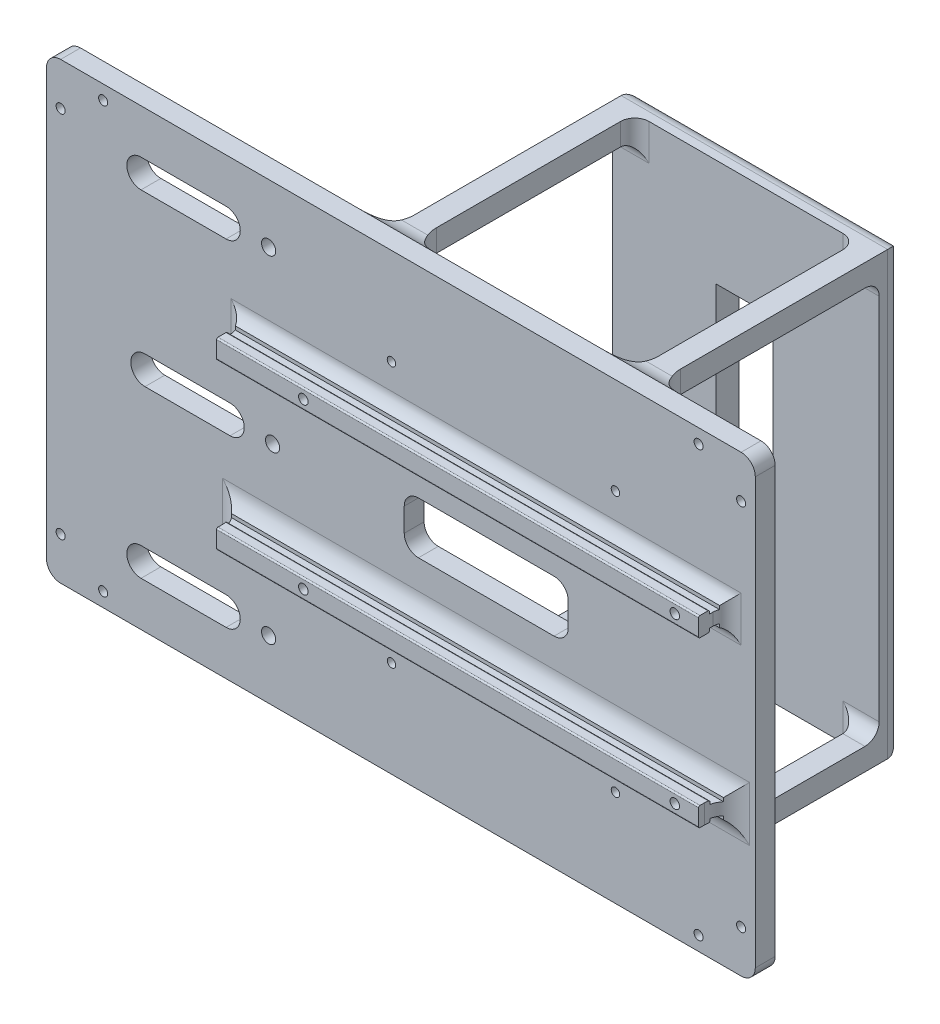
SolidWorks part; units mm, degrees
ref_plane "前视基准面" through (0, 0, 0) normal (0, 0, 1) x (1, 0, 0)
ref_plane "上视基准面" through (0, 0, 0) normal (0, 1, 0) x (1, 0, 0)
ref_plane "右视基准面" through (0, 0, 0) normal (1, 0, 0) x (0, 0, -1)
other "Configuration Table"
sketch "草图1" plane through (0, 0, 0) normal (0, 0, 1) x (1, 0, 0)
  line L0 (0, 0) -> (0, 26371.7997) construction
  line L1 (0, 0) -> (26371.7997, 0) construction
  line L3 (-125, 80) -> (125, 80)
  line L4 (-125, 80) -> (-125, -80)
  line L5 (-125, -80) -> (125, -80)
  line L6 (125, 80) -> (125, -80)
  line L7 (-125, 80) -> (125, -80) construction
  line L8 (-125, -80) -> (125, 80) construction
  point P5 (0, 0)
  dimension "D1" = 250
  dimension "D2" = 160
extrude "凸台-拉伸1" add sketch "草图1" along normal blind 7
sketch "草图2" plane through (0, 0, 7) normal (0, 0, 1) x (1, 0, 0)
  line L0 (0, 0) -> (50000, 0) construction
  line L1 (0, 0) -> (0, 50000) construction
  line L2 (125, -80) -> (125, 80) construction
  line L3 (-55, 32.4) -> (115, 32.4)
  line L4 (-55, 32.4) -> (-55, 25.6)
  line L5 (-55, 25.6) -> (115, 25.6)
  line L6 (115, 32.4) -> (115, 25.6)
  line L7 (-55, 32.4) -> (115, 25.6) construction
  line L8 (-55, 25.6) -> (115, 32.4) construction
  line L9 (-55, -25.6) -> (115, -25.6)
  line L10 (115, -32.4) -> (115, -25.6)
  line L11 (-55, -32.4) -> (-55, -25.6)
  line L12 (-55, -32.4) -> (115, -32.4)
  point P5 (30, 29)
  dimension "D1" = 29
  dimension "D2" = 170
  dimension "D3" = 10
  dimension "D4" = 6.8
extrude "凸台-拉伸2" add sketch "草图2" along normal blind 10
sketch "草图3" plane through (115, 0, 0) normal (1, 0, 0) x (0, 0, -1)
  line L0 (-17, 29) -> (-7, 29) construction
  line L1 (-17, 25.6) -> (-17, 32.4) construction
  line L2 (-7, 25.6) -> (-7, 32.4) construction
  line L3 (-17, 32.4) -> (-7, 32.4) construction
  line L4 (-13.2, 32.4) -> (-10, 32.4)
  line L5 (-13.2, 32.4) -> (-13.2, 31.15)
  line L6 (-13.2, 31.15) -> (-10, 31.15)
  line L7 (-10, 32.4) -> (-10, 31.15)
  line L8 (-13.2, 26.85) -> (-10, 26.85)
  line L9 (-10, 25.6) -> (-10, 26.85)
  line L10 (-13.2, 25.6) -> (-13.2, 26.85)
  line L11 (-13.2, 25.6) -> (-10, 25.6)
  dimension "D1" = 3.8
  dimension "D2" = 3.2
  dimension "D3" = 4.3
extrude "切除-拉伸1" cut sketch "草图3" against normal through all
fillet "圆角1" radius 0.5 4 edges at (30, 25.6, 13.2) (30, 25.6, 17) (30, 32.4, 17) (30, 32.4, 13.2)
sketch "草图4" plane through (115, 0, 0) normal (1, 0, 0) x (0, 0, -1)
  line L0 (-17, -29) -> (-7, -29) construction
  line L1 (-17, -32.4) -> (-17, -25.6) construction
  line L2 (-7, -32.4) -> (-7, -25.6) construction
  line L3 (-17, -25.6) -> (-7, -25.6) construction
  line L4 (-13.2, -25.6) -> (-10, -25.6)
  line L5 (-13.2, -25.6) -> (-13.2, -26.85)
  line L6 (-13.2, -26.85) -> (-10, -26.85)
  line L7 (-10, -25.6) -> (-10, -26.85)
  line L8 (-10, -32.4) -> (-10, -31.15)
  line L9 (-13.2, -31.15) -> (-10, -31.15)
  line L10 (-13.2, -32.4) -> (-13.2, -31.15)
  line L11 (-13.2, -32.4) -> (-10, -32.4)
  dimension "D1" = 3.8
  dimension "D2" = 3.2
  dimension "D3" = 4.3
extrude "切除-拉伸2" cut sketch "草图4" against normal through all
fillet "圆角2" radius 0.5 4 edges at (30, -32.4, 13.2) (30, -32.4, 17) (30, -25.6, 17) (30, -25.6, 13.2)
fillet "圆角3" radius 5 2 edges at (30, 25.6, 7) (30, 32.4, 7)
fillet "圆角4" radius 5 2 edges at (115, 29, 7) (-55, 29, 7)
fillet "圆角5" radius 8 4 edges at (-55, -29, 7) (115, -29, 7) (30, -25.6, 7) (30, -32.4, 7)
sketch "草图5" plane through (0, 0, 0) normal (0, 0, -1) x (-1, 0, 0)
  line L0 (-125, 0) -> (131.1555, 0) construction
  line L1 (-125, -80) -> (-125, 80) construction
  line L2 (-30, 29) -> (-115, 29) construction
  line L3 (-115, 32.4) -> (-115, 25.6) construction
  line L4 (-115, 29) -> (55, 29) construction
  line L5 (55, 32.4) -> (55, 25.6) construction
  circle A0 centre (-106.6, 29) radius 1.675
  circle A1 centre (24.4, 29) radius 1.675
  circle A2 centre (24.4, -29) radius 1.675
  circle A3 centre (-106.6, -29) radius 1.675
  dimension "D1" = 8.4
  dimension "D2" = 3.35
  dimension "D3" = 3.35
  dimension "D4" = 131
extrude "切除-拉伸3" cut sketch "草图5" against normal through all
sketch "草图6" plane through (0, 0, 0) normal (0, 0, -1) x (-1, 0, 0)
  line L0 (-125, 80) -> (-95, 80)
  line L1 (-125, 80) -> (125, 80) construction
  line L2 (-95, 80) -> (-95, 70)
  line L3 (-95, 70) -> (-115, 70)
  line L4 (-115, 70) -> (-115, 60)
  line L5 (-115, 60) -> (-125, 60)
  line L6 (-125, -80) -> (-125, 80) construction
  line L7 (-125, 60) -> (-125, 80)
  line L8 (0, 0) -> (50000, 0) construction
  line L9 (125, 80) -> (95, 80)
  line L10 (95, 80) -> (95, 70)
  line L11 (95, 70) -> (115, 70)
  line L12 (115, 70) -> (115, 60)
  line L13 (115, 60) -> (125, 60)
  line L14 (125, 80) -> (125, -80) construction
  line L15 (125, 60) -> (125, 80)
  line L16 (-125, -60) -> (-125, -80)
  line L17 (-115, -60) -> (-125, -60)
  line L18 (-115, -70) -> (-115, -60)
  line L19 (-95, -70) -> (-115, -70)
  line L20 (-95, -80) -> (-95, -70)
  line L21 (-125, -80) -> (-95, -80)
  line L22 (125, -60) -> (125, -80)
  line L23 (115, -60) -> (125, -60)
  line L24 (115, -70) -> (115, -60)
  line L25 (95, -70) -> (115, -70)
  line L26 (95, -80) -> (95, -70)
  line L27 (125, -80) -> (95, -80)
  circle A0 centre (-120, 65) radius 1.6
  circle A1 centre (-105, 75) radius 1.6
  circle A2 centre (105, 75) radius 1.6
  circle A3 centre (120, 65) radius 1.6
  circle A4 centre (120, -65) radius 1.6
  circle A5 centre (105, -75) radius 1.6
  circle A6 centre (-105, -75) radius 1.6
  circle A7 centre (-120, -65) radius 1.6
  dimension "D9" = 3.2
  dimension "D10" = 5
  dimension "D11" = 5
  dimension "D12" = 3.2
  dimension "D13" = 5
  dimension "D14" = 10
  dimension "D15" = 5
  dimension "D16" = 10
  dimension "D17" = 3.2
  dimension "D18" = 5
  dimension "D19" = 5
  dimension "D20" = 3.2
  dimension "D1" = 30
  dimension "D2" = 20
  dimension "D3" = 10
  dimension "D4" = 10
  dimension "D5" = 30
  dimension "D6" = 20
  dimension "D7" = 10
  dimension "D8" = 10
extrude "切除-拉伸4" cut sketch "草图6" against normal through all contours A5 | A4 | A3 | A2 | A1 | A0 | A7 | A6
sketch "草图8" plane through (0, 0, 0) normal (0, 0, -1) x (-1, 0, 0)
  line L28 (61.653, 64.319) -> (91.653, 64.319)
  line L29 (61.653, 54.319) -> (91.653, 54.319)
  line L38 (61.653, 64.319) -> (61.653, 54.319) construction
  line L39 (91.653, 64.319) -> (91.653, 54.319) construction
  line L40 (61.653, 64.319) -> (91.653, 54.319) construction
  line L41 (61.653, 54.319) -> (91.653, 64.319) construction
  line L64 (60.2593, 4.9129) -> (90.2593, 4.9129)
  line L70 (61.653, -54.319) -> (91.653, -64.319) construction
  line L71 (61.653, -64.319) -> (91.653, -54.319) construction
  line L72 (91.653, -64.319) -> (91.653, -54.319) construction
  line L73 (61.653, -64.319) -> (61.653, -54.319) construction
  line L74 (61.653, -54.319) -> (91.653, -54.319)
  line L75 (61.653, -64.319) -> (91.653, -64.319)
  line L78 (60.2593, -5.0871) -> (90.2593, -5.0871)
  line L79 (60.2593, 4.9129) -> (60.2593, -5.0871) construction
  line L80 (90.2593, 4.9129) -> (90.2593, -5.0871) construction
  line L81 (60.2593, 4.9129) -> (90.2593, -5.0871) construction
  line L82 (60.2593, -5.0871) -> (90.2593, 4.9129) construction
  arc A10 (61.653, 54.319) -> (61.653, 64.319) centre (61.653, 59.319) cw
  arc A11 (91.653, 54.319) -> (91.653, 64.319) centre (91.653, 59.319) ccw
  circle A25 centre (46.653, 59.319) radius 2.5
  circle A36 centre (46.653, -59.319) radius 2.5
  arc A37 (91.653, -54.319) -> (91.653, -64.319) centre (91.653, -59.319) cw
  arc A38 (61.653, -54.319) -> (61.653, -64.319) centre (61.653, -59.319) ccw
  arc A39 (60.2593, -5.0871) -> (60.2593, 4.9129) centre (60.2593, -0.0871) cw
  arc A40 (90.2593, -5.0871) -> (90.2593, 4.9129) centre (90.2593, -0.0871) ccw
  circle A41 centre (45.2593, -0.0871) radius 2.5
  point P0 (75.2593, -0.0871)
  point P9 (-5, -50)
  point P10 (-85, -50)
  point P14 (-5, 50)
  point P17 (-85, 50)
  point P18 (-5, 0)
  point P34 (76.653, -59.319)
  point P41 (76.653, 59.319)
extrude "切除-拉伸5" cut sketch "草图8" against normal through all
fillet "圆角6" radius 5 4 edges at (-125, 80, 3.5) (125, 80, 3.5) (125, -80, 3.5) (-125, -80, 3.5)
sketch "草图9" plane through (0, 0, 0) normal (0, 0, -1) x (-1, 0, 0)
  circle A0 centre (-106.6, 29) radius 3.5
  circle A1 centre (24.4, 29) radius 3.5
  circle A2 centre (-106.6, -29) radius 3.5
  circle A3 centre (24.4, -29) radius 3.5
  dimension "D1" = 7
  dimension "D2" = 7
  dimension "D3" = 7
  dimension "D4" = 7
extrude "切除-拉伸6" cut sketch "草图9" against normal blind 3
sketch "草图15" plane through (0, 0, 0) normal (0, 0, -1) x (-1, 0, 0)
  line L0 (-200000, 0) -> (250000, 0) construction
  line L1 (-97.69, 55) -> (12.31, 55) construction
  line L2 (-97.69, 55) -> (-97.69, -55) construction
  line L3 (-97.69, -55) -> (12.31, -55) construction
  line L4 (12.31, 55) -> (12.31, -55) construction
  line L5 (-97.69, 55) -> (12.31, -55) construction
  line L6 (-97.69, -55) -> (12.31, 55) construction
  line L8 (-75.69, 46) -> (3.31, 46) construction
  line L9 (-75.69, 46) -> (-75.69, -46) construction
  line L10 (-75.69, -46) -> (3.31, -46) construction
  line L11 (3.31, 46) -> (3.31, -46) construction
  line L12 (-75.69, 46) -> (3.31, -46) construction
  line L13 (-75.69, -46) -> (3.31, 46) construction
  circle A0 centre (-75.69, 46) radius 1.5
  circle A1 centre (3.31, 46) radius 1.5
  circle A2 centre (-75.69, -46) radius 1.5
  circle A3 centre (3.31, -46) radius 1.5
  point P0 (-42.69, 0)
  point P8 (-36.19, 0)
  dimension "D3" = 9
  dimension "D1" = 110
  dimension "D2" = 110
  dimension "D4" = 92
  dimension "D5" = 79
extrude "切除-拉伸7" cut sketch "草图15" against normal up to next
sketch "草图17" plane through (0, 0, 0) normal (0, 0, -1) x (-1, 0, 0)
  line L0 (-200000, 0) -> (250000, 0) construction
  line L1 (-97.69, 55) -> (12.31, 55) construction
  line L2 (-97.69, 55) -> (-97.69, -55) construction
  line L3 (-97.69, -55) -> (12.31, -55) construction
  line L4 (12.31, 55) -> (12.31, -55) construction
  line L5 (-97.69, 55) -> (12.31, -55) construction
  line L6 (-97.69, -55) -> (12.31, 55) construction
  line L7 (-26.0576, 0) -> (194.9293, 0) construction
  line L8 (-81.69, 77.8) -> (-73.89, 77.8)
  line L9 (-81.69, 77.8) -> (-81.69, 70)
  line L10 (-81.69, 70) -> (-73.89, 70)
  line L11 (-73.89, 77.8) -> (-73.89, 70)
  line L12 (-81.69, 77.8) -> (-73.89, 70) construction
  line L13 (-81.69, 70) -> (-73.89, 77.8) construction
  line L14 (4.51, -70) -> (12.31, -77.8) construction
  line L15 (4.51, 77.8) -> (12.31, 77.8)
  line L16 (4.51, 77.8) -> (4.51, 70)
  line L17 (4.51, 70) -> (12.31, 70)
  line L18 (12.31, 77.8) -> (12.31, 70)
  line L19 (4.51, 77.8) -> (12.31, 70) construction
  line L20 (4.51, 70) -> (12.31, 77.8) construction
  line L21 (4.51, -77.8) -> (12.31, -70) construction
  line L22 (-81.69, -70) -> (-73.89, -77.8) construction
  line L23 (-81.69, -77.8) -> (-73.89, -70) construction
  line L24 (12.31, -77.8) -> (12.31, -70)
  line L25 (4.51, -70) -> (12.31, -70)
  line L26 (4.51, -77.8) -> (4.51, -70)
  line L27 (4.51, -77.8) -> (12.31, -77.8)
  line L28 (-73.89, -77.8) -> (-73.89, -70)
  line L29 (-81.69, -70) -> (-73.89, -70)
  line L30 (-81.69, -77.8) -> (-81.69, -70)
  line L31 (-81.69, -77.8) -> (-73.89, -77.8)
  circle A0 centre (3.31, 46) radius 1.5 construction
  circle A1 centre (3.31, 46) radius 1.5 construction
  point P0 (-42.69, 0)
  point P10 (-77.79, 73.9)
  point P15 (8.41, 73.9)
  point P30 (8.41, -73.9)
  point P31 (-77.79, -73.9)
  dimension "D1" = 110
  dimension "D2" = 110
  dimension "D3" = 9
  dimension "D4" = 16
  dimension "D5" = 7.8
  dimension "D6" = 7.8
  dimension "D7" = 15
  dimension "D8" = 7.8
  dimension "D9" = 7.8
extrude "凸台-拉伸3" add sketch "草图17" along normal blind 80
sketch "草图18" plane through (0, 0, -80) normal (0, 0, -1) x (-1, 0, 0)
  line L0 (-81.69, 77.8) -> (12.31, 77.8)
  line L1 (12.31, 77.8) -> (12.31, -77.8)
  line L2 (12.31, -77.8) -> (-81.69, -77.8)
  line L3 (-81.69, -77.8) -> (-81.69, 77.8)
extrude "凸台-拉伸4" add sketch "草图18" along normal blind 8
sketch "草图19" plane through (0, 0, -88) normal (0, 0, -1) x (-1, 0, 0)
  line L0 (-80.69, 77.8) -> (12.31, -77.8) construction
  line L4 (-59.19, 50) -> (-9.19, 50) construction
  line L5 (-59.19, 50) -> (-59.19, -50) construction
  line L6 (-59.19, -50) -> (-9.19, -50) construction
  line L7 (-9.19, 50) -> (-9.19, -50) construction
  line L8 (-59.19, 50) -> (-9.19, -50) construction
  line L9 (-59.19, -50) -> (-9.19, 50) construction
  circle A0 centre (-59.19, 50) radius 2
  circle A1 centre (-9.19, 50) radius 2
  circle A2 centre (-59.19, -50) radius 2
  circle A3 centre (-9.19, -50) radius 2
  dimension "D1" = 50
  dimension "D2" = 100
extrude "切除-拉伸8" cut sketch "草图19" against normal blind 5
sketch "草图20" plane through (0, 0, 0) normal (0, 0, -1) x (-1, 0, 0)
  line L0 (-200000, 0) -> (250000, 0) construction
  line L1 (-1.1877, 9.1461) -> (-59.0259, 9.1461)
  line L2 (-1.1877, 9.1461) -> (-1.1877, -9.1461)
  line L3 (-1.1877, -9.1461) -> (-59.0259, -9.1461)
  line L4 (-59.0259, 9.1461) -> (-59.0259, -9.1461)
  line L5 (-1.1877, 9.1461) -> (-59.0259, -9.1461) construction
  line L6 (-1.1877, -9.1461) -> (-59.0259, 9.1461) construction
  point P0 (-30.1068, 0)
extrude "切除-拉伸9" cut sketch "草图20" against normal up to next
fillet "圆角7" radius 5 4 edges at (59.0259, -9.1461, 3.5) (1.1877, -9.1461, 3.5) (59.0259, 9.1461, 3.5) (1.1877, 9.1461, 3.5)
fillet "圆角10" radius 5 2 edges at (73.89, 73.9, -80) (-4.51, 73.9, -80)
fillet "圆角12" radius 5 2 edges at (77.79, -70, -80) (75.29, 70, -80)
fillet "圆角13" radius 5 4 edges at (-5.91, 70, -80) (-4.51, -73.9, -80) (-8.41, -70, -80) (73.89, -71.4, -80)
fillet "圆角14" radius 5 4 edges at (34.69, -77.8, -88) (81.69, 0, -88) (-12.31, 0, -88) (34.69, 77.8, -88)
sketch "草图21" plane through (0, 0, -88) normal (0, 0, -1) x (-1, 0, 0)
  line L0 (-200000, 0) -> (250000, 0) construction
  line L1 (-44.19, 40) -> (-24.19, 40)
  line L2 (-44.19, 40) -> (-44.19, -40)
  line L3 (-44.19, -40) -> (-24.19, -40)
  line L4 (-24.19, 40) -> (-24.19, -40)
  line L5 (-44.19, 40) -> (-24.19, -40) construction
  line L6 (-44.19, -40) -> (-24.19, 40) construction
  line L7 (-59.19, 50) -> (-9.19, 50) construction
  line L8 (-34.19, 50) -> (-34.19, 84.7538) construction
  point P0 (-34.19, 0)
  dimension "D1" = 20
  dimension "D2" = 80
extrude "切除-拉伸10" cut sketch "草图21" against normal up to next
fillet "圆角15" radius 10 16 edges at (-12.31, 73.9, 0) (-8.41, 77.8, 0) (81.69, 73.9, 0) (77.79, 77.8, 0) (-8.41, -77.8, 0) (-4.51, -73.9, 0) (77.79, -77.8, 0) (81.69, -73.9, 0) (-8.41, 70, 0) (-4.51, 73.9, 0) (77.79, 70, 0) (73.89, 73.9, 0) (77.79, -70, 0) (73.89, -73.9, 0) (-8.41, -70, 0) (-12.31, -73.9, 0)
ref_plane "基准面1" through (73.89, 77.8, -75) normal (0, 0, 1) x (1, 0, 0)
